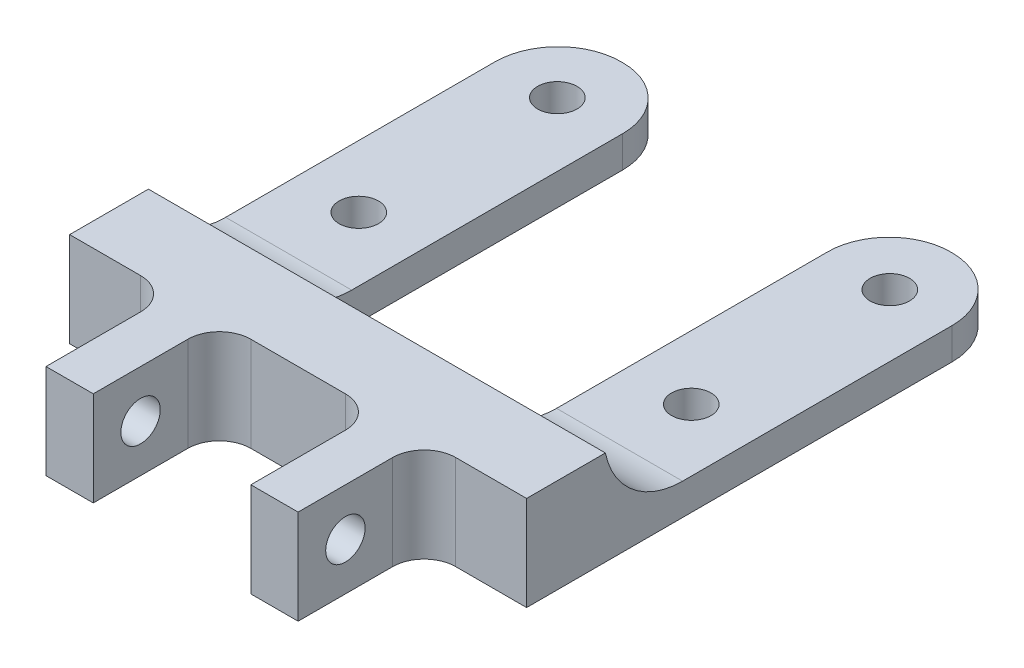
SolidWorks part; units mm, degrees
ref_plane "Front Plane" through (0, 0, 0) normal (0, 0, 1) x (1, 0, 0)
ref_plane "Top Plane" through (0, 0, 0) normal (0, 1, 0) x (1, 0, 0)
ref_plane "Right Plane" through (0, 0, 0) normal (1, 0, 0) x (0, 0, -1)
sketch "Sketch1" plane through (0, 0, 0) normal (0, 1, 0) x (1, 0, 0)
  line L0 (24.9, 26) -> (25, 26)
  line L1 (0, 0) -> (29, 0)
  line L2 (0, 0) -> (0, 22)
  line L3 (4, 26) -> (4.1, 26)
  line L4 (29, 0) -> (29, 22)
  line L6 (8, 22.1) -> (8, 3.5)
  line L7 (8, 3.5) -> (21, 3.5)
  line L8 (21, 22.1) -> (21, 3.5)
  circle A0 centre (3.95, 22) radius 1.25
  circle A1 centre (25.05, 22) radius 1.25
  circle A2 centre (25.05, 9.4) radius 1.25
  circle A3 centre (3.95, 9.4) radius 1.25
  arc A4 (0, 22) -> (4, 26) centre (4, 22) cw
  arc A5 (25, 26) -> (29, 22) centre (25, 22) cw
  arc A6 (24.9, 26) -> (21, 22.1) centre (24.9, 22.1) ccw
  arc A7 (4.1, 26) -> (8, 22.1) centre (4.1, 22.1) cw
  point P19 (0, 26)
  point P22 (29, 26)
  dimension "D7" = 2.5
  dimension "D8" = 2.5
  dimension "D9" = 2.5
  dimension "D10" = 2.5
  dimension "D18" = 4
  dimension "D19" = 3.9
  dimension "D1" = 29
  dimension "D2" = 26
  dimension "D3" = 21.1
  dimension "D4" = 3.95
  dimension "D5" = 21.1
  dimension "D6" = 3.95
  dimension "D11" = 9.4
  dimension "D12" = 9.4
  dimension "D13" = 12.6
  dimension "D14" = 12.6
  dimension "D15" = 8
  dimension "D16" = 8
  dimension "D17" = 3.5
extrude "Boss-Extrude1" add sketch "Sketch1" along normal blind 2 contours L3 L8 L7 L6 L2 L1 L4 A3 A2 A1 A0 region at (24.95, 0, -25.6105)
sketch "Sketch2" plane through (0, 2, 0) normal (0, 1, 0) x (1, 0, 0)
  line L1 (0, 0) -> (29, 0)
  line L2 (0, 0) -> (0, -5)
  line L3 (0, -5) -> (29, -5)
  line L4 (29, 0) -> (29, -5)
  dimension "D1" = 5
extrude "Boss-Extrude2" add sketch "Sketch2" along normal blind 4 and the other way blind 2
fillet "Fillet1" radius 5 1 edges at (14.5, 2, 0)
sketch "Sketch3" plane through (0, 0, 5) normal (0, 0, 1) x (1, 0, 0)
  line L0 (0, 6) -> (29, 6) construction
  line L1 (9.5, 6) -> (6.5, 6)
  line L2 (9.5, 6) -> (9.5, 0)
  line L3 (9.5, 0) -> (6.5, 0)
  line L4 (6.5, 6) -> (6.5, 0)
  line L5 (0, 0) -> (29, 0) construction
  line L7 (0, 0) -> (0, 6) construction
  line L8 (29, 0) -> (29, 6) construction
  line L9 (19.5, 0) -> (22.5, 0)
  line L10 (19.5, 0) -> (19.5, 6)
  line L11 (19.5, 6) -> (22.5, 6)
  line L12 (22.5, 0) -> (22.5, 6)
  dimension "D1" = 3
  dimension "D2" = 6.5
  dimension "D3" = 6.5
  dimension "D4" = 3
extrude "Boss-Extrude3" add sketch "Sketch3" along normal blind 8
fillet "Fillet2" radius 2 4 edges at (9.5, 3, 5) (6.5, 3, 5) (19.5, 3, 5) (22.5, 3, 5)
sketch "Sketch4" plane through (9.5, 0, 0) normal (1, 0, 0) x (0, 0, -1)
  line L0 (-13, 6) -> (-7, 6) construction
  line L1 (-7, 0) -> (-7, 6) construction
  circle A0 centre (-10, 3) radius 1.25
  dimension "D3" = 2.5
  dimension "D1" = 3
  dimension "D2" = 3
extrude "Cut-Extrude1" cut sketch "Sketch4" against normal blind 7 and the other way blind 15
